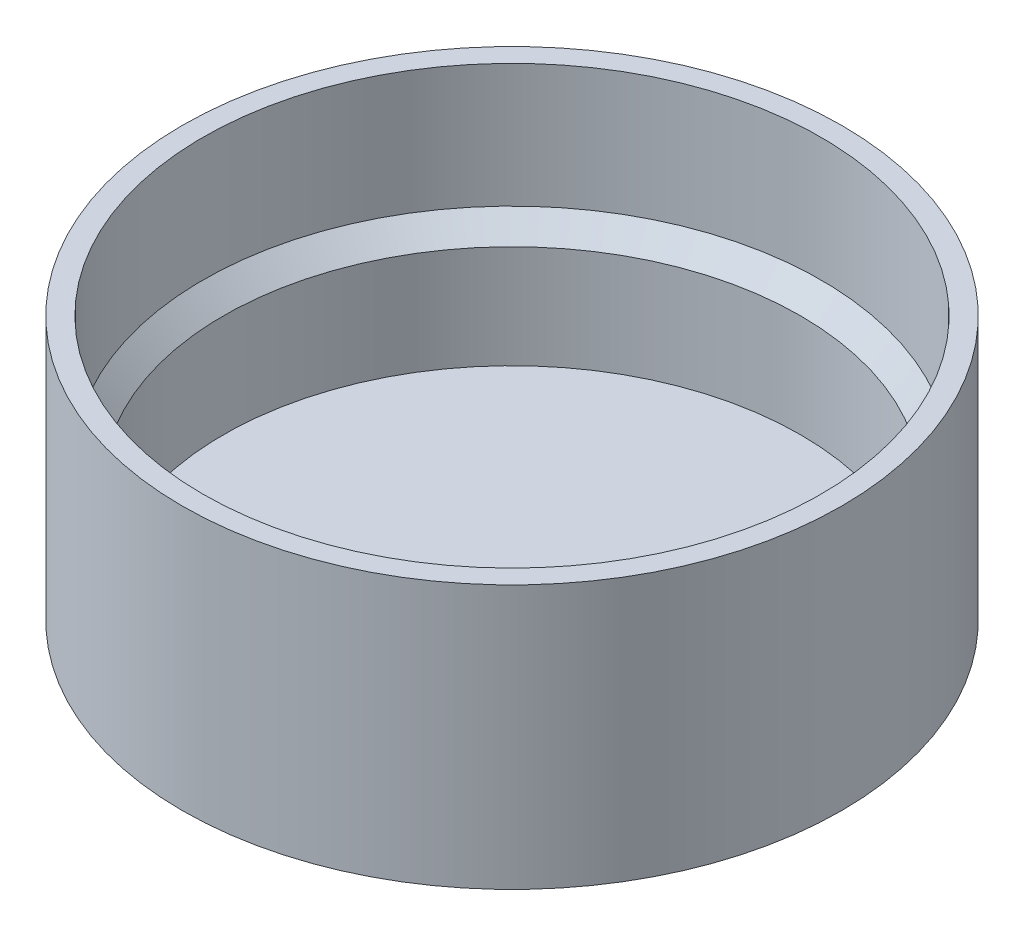
SolidWorks part; units mm, degrees
ref_plane "Alzado" through (0, 0, 0) normal (0, 0, 1) x (1, 0, 0)
ref_plane "Planta" through (0, 0, 0) normal (0, 1, 0) x (1, 0, 0)
ref_plane "Vista lateral" through (0, 0, 0) normal (1, 0, 0) x (0, 0, -1)
sketch "Croquis1" plane through (0, 0, 0) normal (0, 1, 0) x (1, 0, 0)
  circle A0 centre (0, 0) radius 40
extrude "Saliente-Extruir1" add sketch "Croquis1" along normal blind 2
sketch "Croquis2" plane through (0, 2, 0) normal (0, 1, 0) x (1, 0, 0)
  line L0 (-35, 0) -> (35, 0)
  circle A1 centre (0, 0) radius 35
  circle A2 centre (0, 0) radius 40
  circle A3 centre (0, 0) radius 40
  circle M3 centre (0, 0) radius 40
  dimension "D1" = 0
  dimension "D2" = 5
extrude "Saliente-Extruir2" add sketch "Croquis2" along normal blind 30 contours A1 M3 region at (-38.8686, 2, 0)
sketch "Croquis3" plane through (0, 32, 0) normal (0, 1, 0) x (1, 0, 0)
  circle A2 centre (0, 0) radius 37.5
  circle A3 centre (0, 0) radius 37.5
  circle A5 centre (0, 0) radius 35
  circle A6 centre (0, 0) radius 35
  dimension "D1" = 2.5
  dimension "D2" = 0
extrude "Cortar-Extruir1" cut sketch "Croquis3" against normal blind 15
chamfer "Chaflán1" distance 2.5 angle 45 1 edges at (0, 17, 35)
